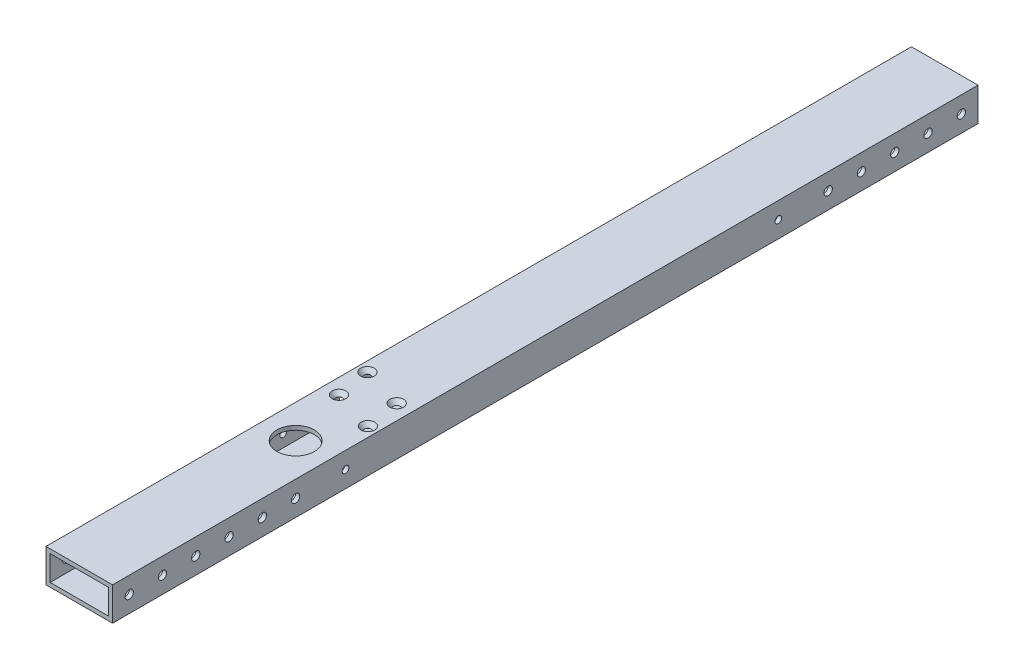
SolidWorks part; units mm, degrees
material "6061 Alloy"
ref_plane "Front Plane" through (0, 0, 0) normal (0, 0, 1) x (1, 0, 0)
ref_plane "Top Plane" through (0, 0, 0) normal (0, 1, 0) x (1, 0, 0)
ref_plane "Right Plane" through (0, 0, 0) normal (1, 0, 0) x (0, 0, -1)
sketch "Sketch1" plane through (0, 0, 0) normal (0, 0, 1) x (1, 0, 0)
  line L0 (-22.225, 9.525) -> (22.225, 9.525)
  line L2 (-25.4, 12.7) -> (25.4, 12.7)
  line L3 (-25.4, 12.7) -> (-25.4, -12.7)
  line L4 (-25.4, -12.7) -> (25.4, -12.7)
  line L5 (25.4, 12.7) -> (25.4, -12.7)
  line L10 (22.225, 9.525) -> (22.225, -9.525)
  line L11 (-22.225, -9.525) -> (22.225, -9.525)
  line L12 (-22.225, 9.525) -> (-22.225, -9.525)
  point P12 (0, 12.7)
  point P14 (25.4, 0)
  dimension "Wall Thickness" = 3.175
  dimension "Outside Width" = 50.8
  dimension "Outside Height" = 25.4
  dimension "Inside Height" = 19.05
  dimension "Inside Width" = 44.45
sketch "Sketch2" plane through (0, 0, 0) normal (1, 0, 0) x (0, 0, -1)
  line L0 (330.2, 0) -> (-330.2, 0)
  point P4 (0, 0)
  point P7 (-330.2, 0)
  point P10 (330.2, 0)
  dimension "Length" = 660.4
sketch "Sketch3" plane through (0, 0, 0) normal (0, 0, 1) x (1, 0, 0)
  line L21 (25.4, 12.7) -> (-25.4, 12.7)
  line L22 (25.4, -12.7) -> (25.4, 12.7)
  line L23 (-25.4, -12.7) -> (25.4, -12.7)
  line L24 (-25.4, 12.7) -> (-25.4, -12.7)
  line L25 (25.4, 12.7) -> (-25.4, 12.7)
  line L26 (25.4, -12.7) -> (25.4, 12.7)
  line L27 (-25.4, -12.7) -> (25.4, -12.7)
  line L28 (-25.4, 12.7) -> (-25.4, -12.7)
  line L29 (22.225, 9.525) -> (-22.225, 9.525)
  line L30 (22.225, -9.525) -> (22.225, 9.525)
  line L31 (-22.225, -9.525) -> (22.225, -9.525)
  line L32 (-22.225, 9.525) -> (-22.225, -9.525)
  line L33 (22.225, 9.525) -> (-22.225, 9.525)
  line L34 (22.225, -9.525) -> (22.225, 9.525)
  line L35 (-22.225, -9.525) -> (22.225, -9.525)
  line L36 (-22.225, 9.525) -> (-22.225, -9.525)
  dimension "D1" = 0
  dimension "D2" = 0
extrude "Boss-Extrude1" add sketch "Sketch3" along normal up to vertex (330.2 mm away) and the other way up to vertex (330.2 mm away) up to point (0, 0, 330.2) other way up to point (0, 0, -330.2)
sketch "Drawing Reference" plane through (0, 0, 0) normal (1, 0, 0) x (0, 0, -1)
  line L0 (-330.2, 0) -> (330.2, 0) construction
  line L1 (0, -12.7) -> (0, 12.7) construction
  line L2 (-330.2, -12.7) -> (330.2, -12.7) construction
  line L5 (-330.2, 12.7) -> (330.2, 12.7) construction
  point P7 (-293.624, 0)
  point P8 (293.624, 0)
  dimension "D1" = 36.576
sketch "Sketch5" plane through (25.4, 0, 0) normal (1, 0, 0) x (0, 0, -1)
  line L2 (-266.7, 0) -> (-241.3, 0)
  line L3 (-241.3, 0) -> (-215.9, 0)
  line L4 (-215.9, 0) -> (-190.5, 0)
  line L5 (-317.5, 0) -> (-330.2, 0)
  line L6 (-330.2, -12.7) -> (-330.2, 12.7) construction
  line L7 (-317.5, 0) -> (-292.1, 0)
  line L8 (-292.1, 0) -> (-266.7, 0)
sketch "Sketch8" plane through (25.4, 0, 0) normal (1, 0, 0) x (0, 0, -1)
  line L0 (330.2, 0) -> (292.1, 0)
  line L1 (330.2, -12.7) -> (330.2, 12.7) construction
  line L2 (292.1, 0) -> (266.7, 0)
  line L3 (266.7, 0) -> (241.3, 0)
  line L4 (241.3, 0) -> (215.9, 0)
  line L5 (330.2, 0) -> (317.5, 0)
hole_wizard "1/4 (0.25) Diameter Hole3" positions "Sketch12" profile "Sketch13" hole size "1/4" standard "ANSI Inch" end condition through all
sketch "Sketch12" plane through (-25.4, 0, 0) normal (-1, 0, 0) x (0, 0, 1)
  point P4 (-317.5, 0)
sketch "Sketch13" plane through (-25.4, 0, -317.5) normal (0, 1, 0) x (0, 0, 1)
  line L0 (0, 0) -> (0, 50.8)
  line L1 (0, 50.8) -> (3.175, 50.8)
  line L2 (3.175, 50.8) -> (3.175, 0)
  line L5 (3.175, 0) -> (0, 0)
  line L11 (0, -6.35) -> (0, 107.95) construction
  dimension "Thru Hole Dia." = 6.35
  dimension "Thru Hole Depth" = 50.8
hole_wizard "1/4 (0.25) Diameter Hole4" positions "Sketch14" profile "Sketch15" hole size "1/4" standard "ANSI Inch" end condition through all
sketch "Sketch14" plane through (-25.4, 0, 0) normal (-1, 0, 0) x (0, 0, 1)
  point P0 (292.1, 0)
  point P3 (317.5, 0)
sketch "Sketch15" plane through (-25.4, 0, 292.1) normal (0, 1, 0) x (0, 0, 1)
  line L0 (0, 0) -> (0, 50.8)
  line L1 (0, 50.8) -> (3.175, 50.8)
  line L2 (3.175, 50.8) -> (3.175, 0)
  line L5 (3.175, 0) -> (0, 0)
  line L11 (0, -6.35) -> (0, 107.95) construction
  dimension "Thru Hole Dia." = 6.35
  dimension "Thru Hole Depth" = 50.8
hole_wizard "1/4 (0.25) Diameter Hole5" positions "Sketch17" profile "Sketch18" hole size "1/4" standard "ANSI Inch" end condition through all
sketch "Sketch17" plane through (25.4, 0, 0) normal (1, 0, 0) x (0, 0, -1)
  point P0 (292.1, 0)
  point P3 (266.7, 0)
sketch "Sketch18" plane through (25.4, 0, -292.1) normal (0, 1, 0) x (0, 0, -1)
  line L0 (0, 0) -> (0, 50.8)
  line L1 (0, 50.8) -> (3.175, 50.8)
  line L2 (3.175, 50.8) -> (3.175, 0)
  line L5 (3.175, 0) -> (0, 0)
  line L11 (0, -6.35) -> (0, 107.95) construction
  dimension "Thru Hole Dia." = 6.35
  dimension "Thru Hole Depth" = 50.8
hole_wizard "1/4 (0.25) Diameter Hole6" positions "Sketch19" profile "Sketch20" hole size "1/4" standard "ANSI Inch" end condition through all
sketch "Sketch19" plane through (25.4, 0, 0) normal (1, 0, 0) x (0, 0, -1)
  point P0 (215.9, 0)
  point P3 (241.3, 0)
sketch "Sketch20" plane through (25.4, 0, -215.9) normal (0, 1, 0) x (0, 0, -1)
  line L0 (0, 0) -> (0, 50.8)
  line L1 (0, 50.8) -> (3.175, 50.8)
  line L2 (3.175, 50.8) -> (3.175, 0)
  line L5 (3.175, 0) -> (0, 0)
  line L11 (0, -6.35) -> (0, 107.95) construction
  dimension "Thru Hole Dia." = 6.35
  dimension "Thru Hole Depth" = 50.8
hole_wizard "1/4 (0.25) Diameter Hole7" positions "Sketch21" profile "Sketch22" hole size "1/4" standard "ANSI Inch" end condition through all
sketch "Sketch21" plane through (25.4, 0, 0) normal (1, 0, 0) x (0, 0, -1)
  point P0 (-190.5, 0)
  point P3 (-215.9, 0)
sketch "Sketch22" plane through (25.4, 0, 190.5) normal (0, 1, 0) x (0, 0, -1)
  line L0 (0, 0) -> (0, 50.8)
  line L1 (0, 50.8) -> (3.175, 50.8)
  line L2 (3.175, 50.8) -> (3.175, 0)
  line L5 (3.175, 0) -> (0, 0)
  line L11 (0, -6.35) -> (0, 107.95) construction
  dimension "Thru Hole Dia." = 6.35
  dimension "Thru Hole Depth" = 50.8
hole_wizard "1/4 (0.25) Diameter Hole8" positions "Sketch23" profile "Sketch24" hole size "1/4" standard "ANSI Inch" end condition through all
sketch "Sketch23" plane through (25.4, 0, 0) normal (1, 0, 0) x (0, 0, -1)
  point P0 (-266.7, 0)
  point P3 (-241.3, 0)
sketch "Sketch24" plane through (25.4, 0, 266.7) normal (0, 1, 0) x (0, 0, -1)
  line L0 (0, 0) -> (0, 50.8)
  line L1 (0, 50.8) -> (3.175, 50.8)
  line L2 (3.175, 50.8) -> (3.175, 0)
  line L5 (3.175, 0) -> (0, 0)
  line L11 (0, -6.35) -> (0, 107.95) construction
  dimension "Thru Hole Dia." = 6.35
  dimension "Thru Hole Depth" = 50.8
sketch "Sketch25" plane through (25.4, 0, 0) normal (1, 0, 0) x (0, 0, -1)
  line L0 (-190.5, 0) -> (-152.4, 0)
  line L1 (215.9, 0) -> (177.8, 0)
hole_wizard "13/64 (0.20313) Diameter Hole1" positions "Sketch26" profile "Sketch27" hole size "13/64" standard "ANSI Inch" end condition through all
sketch "Sketch26" plane through (25.4, 0, 0) normal (1, 0, 0) x (0, 0, -1)
  point P0 (-152.4, 0)
  point P3 (177.8, 0)
sketch "Sketch27" plane through (25.4, 0, 152.4) normal (0, 1, 0) x (0, 0, -1)
  line L0 (0, 0) -> (0, 50.8)
  line L1 (0, 50.8) -> (2.5798, 50.8)
  line L2 (2.5798, 50.8) -> (2.5798, 0)
  line L5 (2.5798, 0) -> (0, 0)
  line L11 (0, -6.35) -> (0, 107.95) construction
  dimension "Thru Hole Dia." = 5.1595
  dimension "Thru Hole Depth" = 50.8
sketch "Sketch30" plane through (-25.4, 0, 0) normal (-1, 0, 0) x (0, 0, 1)
  point P0 (-128.5875, 0)
  point P1 (-103.1875, 0)
  point P2 (77.7875, 0)
  point P3 (103.1875, 0)
hole_wizard "1/2 (0.5) Diameter Hole1" positions "Sketch33" profile "Sketch34" hole size "1/2" standard "ANSI Inch"
sketch "Sketch33" plane through (-25.4, 0, 0) normal (-1, 0, 0) x (0, 0, 1)
  point P0 (-128.5875, 0)
  point P3 (-103.1875, 0)
  point P7 (77.7875, 0)
  point P10 (103.1875, 0)
sketch "Sketch34" plane through (-25.4, 0, -128.5875) normal (0, 1, 0) x (0, 0, 1)
  line L0 (0, 0) -> (0, 10.1655)
  line L1 (0, 10.1655) -> (6.35, 6.35)
  line L2 (6.35, 6.35) -> (6.35, 0)
  line L5 (6.35, 0) -> (0, 0)
  line L10 (0, 10.1655) -> (-6.35, 6.35) construction
  line L11 (0, -6.35) -> (0, 107.95) construction
  dimension "Hole Dia." = 12.7
  dimension "Hole Depth" = 6.35
  dimension "Drill Angle" = 118
sketch "Sketch36" plane through (0, -12.7, 0) normal (0, -1, 0) x (1, 0, 0)
  line L0 (-25.4, 165.1081) -> (25.4, 165.1081) construction
  line L1 (-25.4, 330.2) -> (-25.4, -330.2) construction
  line L2 (25.4, 330.2) -> (25.4, -330.2) construction
  line L3 (0, 165.1081) -> (7.7998, 138.8083) construction
  line L5 (7.7998, 138.8083) -> (-2.7234, 135.6874) construction
  line L6 (-25.544, 128.9314) -> (574.9671, 306.8109) construction
  circle A0 centre (0, 165.1081) radius 14.2875
  dimension "D2" = 28.575
  dimension "D1" = 27.432
extrude "Cut-Extrude1" cut sketch "Sketch36" against normal through all
sketch "Sketch37" plane through (0, -12.7, 0) normal (0, -1, 0) x (1, 0, 0)
  line L1 (13.819, 101.7821) -> (17.931, 127.883) construction
  line L5 (-13.819, 118.2319) -> (17.931, 127.883) construction
  line L6 (-17.931, 92.3773) -> (13.819, 101.7821) construction
  line L7 (-13.819, 118.2319) -> (-17.931, 92.3773) construction
hole_wizard "#10 Clearance Hole4" positions "Sketch45" profile "Sketch46" hole size "#10" standard "ANSI Inch" end condition through all
sketch "Sketch45" plane through (0, -12.7, 0) normal (0, -1, 0) x (-1, 0, 0)
  point P0 (-13.819, -101.7821)
  point P3 (-17.931, -127.883)
  point P6 (13.819, -118.2319)
  point P9 (17.931, -92.3773)
sketch "Sketch46" plane through (13.819, -12.7, 101.7821) normal (1, 0, 0) x (0, 0, -1)
  line L0 (0, 0) -> (0, 25.4)
  line L1 (0, 25.4) -> (5.2197, 25.4)
  line L2 (2.4892, 22.2589) -> (2.4892, 0)
  line L5 (2.4892, 0) -> (0, 0)
  line L7 (5.2197, 25.4) -> (2.4892, 22.2589)
  line L8 (-5.2197, 25.4) -> (-2.4892, 22.2589) construction
  line L11 (0, -6.35) -> (0, 107.95) construction
  dimension "Thru Hole Dia." = 4.9784
  dimension "Thru Hole Depth" = 25.4
  dimension "Far C'Sink Dia." = 10.4394
  dimension "Far C'Sink Angle" = 82
equation "\"D1@Drawing Reference\"=\"Outside Width@Sketch1\" * 0.72"
